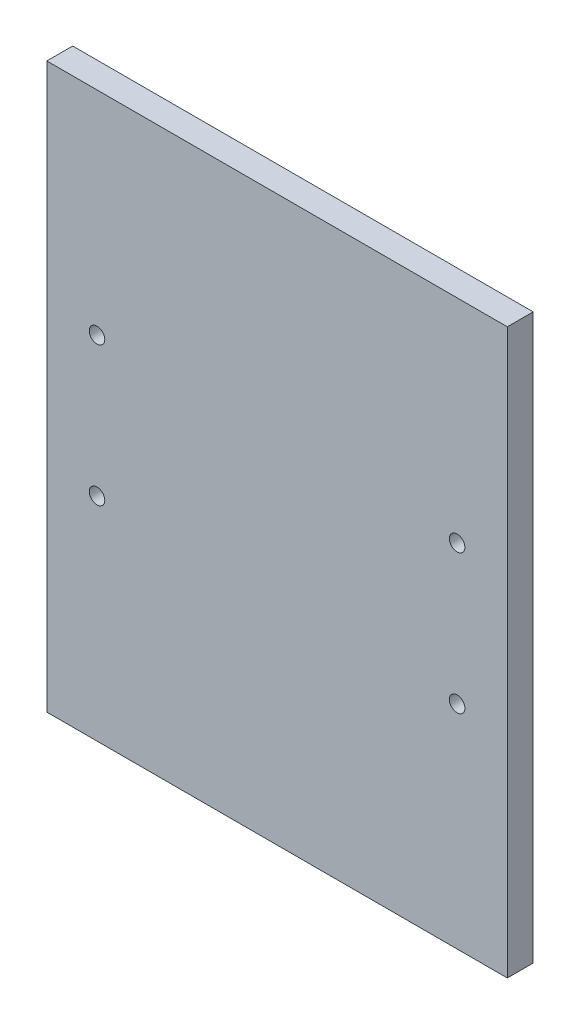
SolidWorks part; units mm, degrees
ref_plane "Front Plane" through (0, 0, 0) normal (0, 0, 1) x (1, 0, 0)
ref_plane "Top Plane" through (0, 0, 0) normal (0, 1, 0) x (1, 0, 0)
ref_plane "Right Plane" through (0, 0, 0) normal (1, 0, 0) x (0, 0, -1)
sketch "Sketch1" plane through (0, 0, 0) normal (0, 0, 1) x (1, 0, 0)
  line L1 (-44.5, -54.5) -> (44.5, -54.5)
  line L2 (-44.5, -54.5) -> (-44.5, 54.5)
  line L3 (-44.5, 54.5) -> (44.5, 54.5)
  line L4 (44.5, -54.5) -> (44.5, 54.5)
  line L5 (-44.5, -54.5) -> (44.5, 54.5) construction
  line L6 (-44.5, 54.5) -> (44.5, -54.5) construction
  point P0 (0, 0)
  dimension "D1" = 89
  dimension "D2" = 109
extrude "Boss-Extrude1" add sketch "Sketch1" along normal blind 5
sketch "Sketch2" plane through (0, 0, 5) normal (0, 0, 1) x (1, 0, 0)
  circle A0 centre (-34.8, 13.46) radius 1.5
  circle A1 centre (34.8, 13.46) radius 1.5
  circle A2 centre (34.8, -13.46) radius 1.5
  circle A3 centre (-34.8, -13.46) radius 1.5
  dimension "D1" = 3
  dimension "D5" = 2
  dimension "D2" = 13.46
  dimension "D4" = 34.8
  dimension "D3" = 2
extrude "Cut-Extrude1" cut sketch "Sketch2" against normal blind 5
